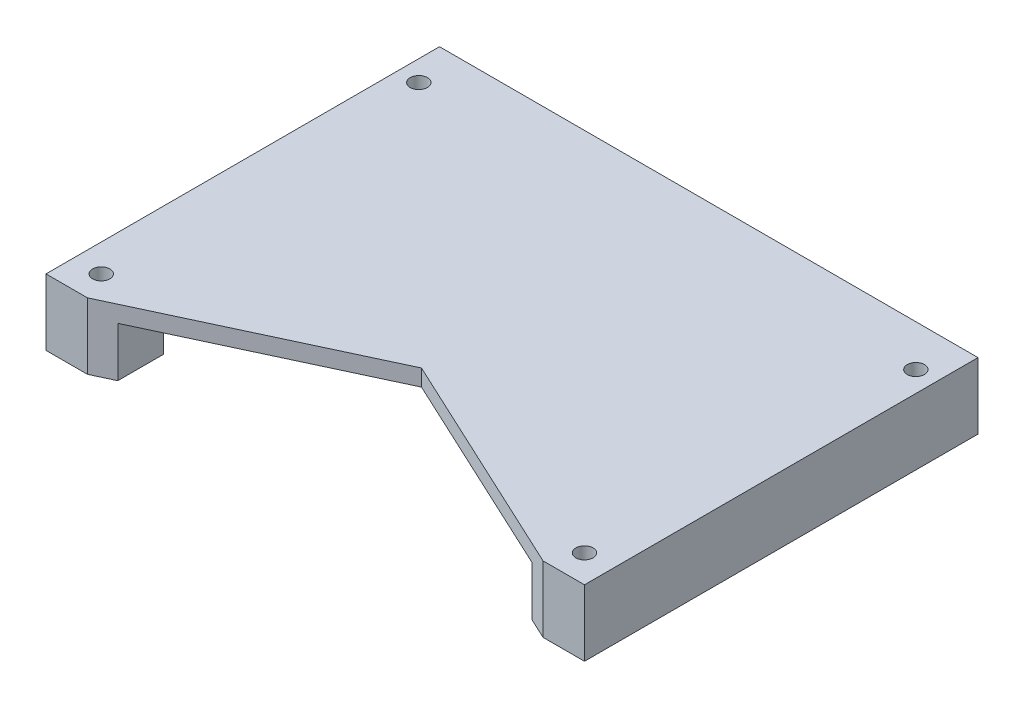
SolidWorks part; units mm, degrees
ref_plane "Front Plane" through (0, 0, 0) normal (0, 0, 1) x (1, 0, 0)
ref_plane "Top Plane" through (0, 0, 0) normal (0, 1, 0) x (1, 0, 0)
ref_plane "Right Plane" through (0, 0, 0) normal (1, 0, 0) x (0, 0, -1)
sketch "Sketch1" plane through (0, 0, 0) normal (0, 1, 0) x (1, 0, 0)
  line L1 (0, 0) -> (78, 0)
  line L2 (0, 0) -> (0, 57)
  line L3 (0, 57) -> (78, 57)
  line L4 (78, 0) -> (78, 57)
  dimension "D1" = 57
  dimension "D2" = 78
extrude "Boss-Extrude1" add sketch "Sketch1" along normal blind 9.6
sketch "Sketch2" plane through (0, 0, 0) normal (0, -1, 0) x (1, 0, 0)
  line L0 (78, -57) -> (0, -57) construction
  line L1 (6, -57) -> (72, -57)
  line L2 (6, -57) -> (6, -8)
  line L3 (6, -8) -> (72, -8)
  line L4 (72, -57) -> (72, -8)
  line L5 (0, -57) -> (0, 0) construction
  line L6 (78, 0) -> (78, -57) construction
  dimension "D1" = 6
  dimension "D2" = 6
  dimension "D3" = 49
extrude "Cut-Extrude1" cut sketch "Sketch2" against normal blind 7.2
sketch "Sketch3" plane through (0, 0, 0) normal (0, -1, 0) x (1, 0, 0)
  line L0 (72, -8) -> (6, -8) construction
  line L1 (9, -8) -> (69, -8)
  line L2 (9, -8) -> (9, 0)
  line L3 (9, 0) -> (69, 0)
  line L4 (69, -8) -> (69, 0)
  line L5 (0, 0) -> (78, 0) construction
  line L6 (0, -57) -> (0, 0) construction
  line L7 (78, 0) -> (78, -57) construction
  dimension "D1" = 9
  dimension "D2" = 9
extrude "Cut-Extrude2" cut sketch "Sketch3" against normal up to surface (7.2 mm away) up to face at (39, 7.2, -32.5)
sketch "Sketch4" plane through (0, 9.6, 0) normal (0, 1, 0) x (1, 0, 0)
  line L0 (0, 0) -> (78, 0) construction
  line L1 (6, 0) -> (39, 15.3882)
  line L2 (39, 15.3882) -> (72, 0)
  line L3 (39, 15.3882) -> (39, 57) construction
  line L4 (72, 0) -> (6, 0)
  line L5 (78, 57) -> (0, 57) construction
  dimension "D1" = 130
  dimension "D2" = 6
extrude "Cut-Extrude3" cut sketch "Sketch4" against normal up to next
hole_wizard "Tap Drill for M3 Tap1" positions "Sketch6" profile "Sketch5" hole size "M3" standard "ISO" end condition up to next
sketch "Sketch6" plane through (0, 0, 0) normal (0, -1, 0) x (-1, 0, 0)
  line L0 (-78, 57) -> (-72, 57) construction
  line L1 (-6, 57) -> (0, 57) construction
  line L2 (-72, 0) -> (-78, 0) construction
  line L3 (-78, 0) -> (-78, 57) construction
  line L5 (0, 57) -> (0, 0) construction
  point P0 (-4, 4)
  point P2 (-3, 51)
  point P4 (-74, 4)
  point P6 (-75, 51)
  dimension "D1" = 6
  dimension "D2" = 6
  dimension "D3" = 4
  dimension "D4" = 4
  dimension "D5" = 4
  dimension "D6" = 3
  dimension "D7" = 3
sketch "Sketch5" plane through (4, 0, -4) normal (1, 0, 0) x (0, 0, -1)
  line L0 (0, 0) -> (0, 9.6)
  line L1 (0, 9.6) -> (1.25, 9.6)
  line L2 (1.25, 9.6) -> (1.25, 0)
  line L5 (1.25, 0) -> (0, 0)
  line L11 (0, -6.35) -> (0, 107.95) construction
  dimension "Thru Hole Dia." = 2.5
  dimension "Thru Hole Depth" = 9.6
